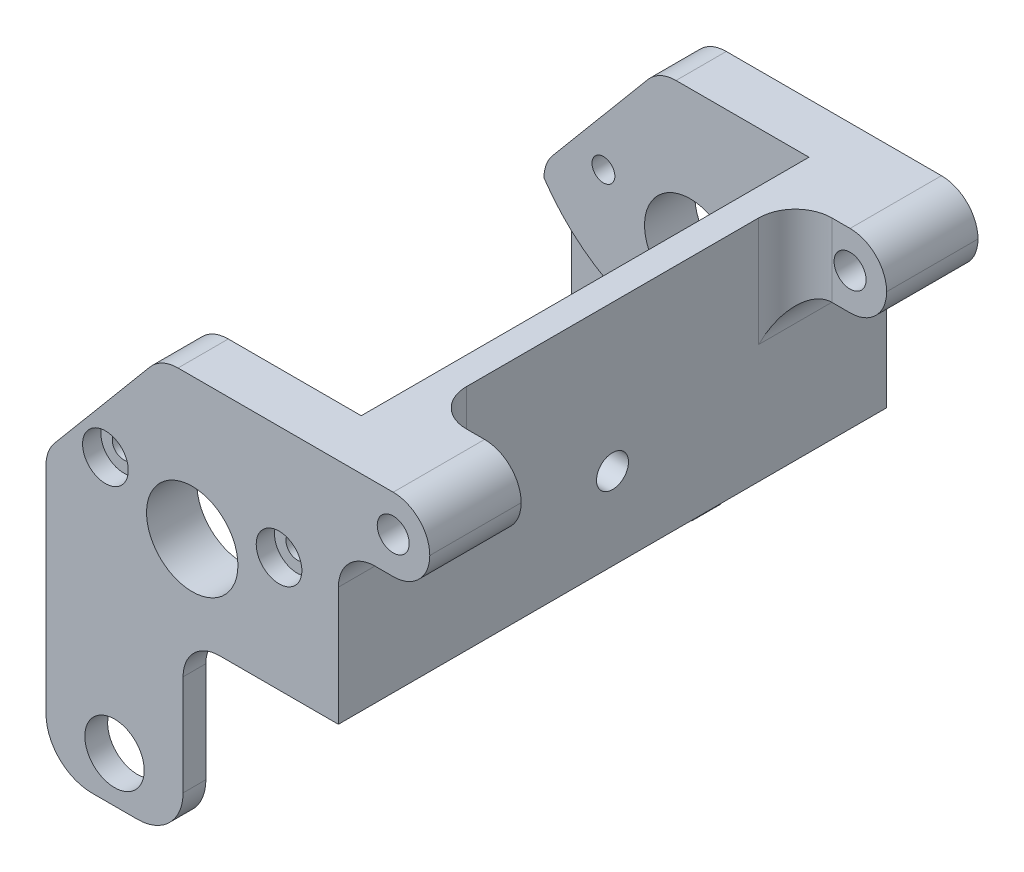
SolidWorks part; units mm, degrees
ref_plane "Front Plane" through (0, 0, 0) normal (0, 0, 1) x (1, 0, 0)
ref_plane "Top Plane" through (0, 0, 0) normal (0, 1, 0) x (1, 0, 0)
ref_plane "Right Plane" through (0, 0, 0) normal (1, 0, 0) x (0, 0, -1)
sketch "Sketch2" plane through (0, 0, 0) normal (0, 0, 1) x (1, 0, 0)
  line L0 (-7.5, 5) -> (-7.5, 30)
  line L1 (-7.5, 30) -> (5.0865, 45)
  line L2 (5.0865, 45) -> (24.5, 45)
  line L3 (24.5, 45) -> (24.5, 20)
  line L4 (24.5, 20) -> (7.5, 20)
  line L5 (7.5, 20) -> (7.5, 5)
  line L6 (-2.5, 0) -> (2.5, 0)
  line L7 (-7.5, 0) -> (7.5, 0) construction
  line L8 (-7.5, 5) -> (7.5, 5) construction
  line L9 (18.0048, 32.5697) -> (-0.9952, 32.5697) construction
  line L10 (8.5048, 32.5697) -> (8.5048, 29.5697) construction
  line L11 (0, 5) -> (8.5048, 29.5697) construction
  circle A5 centre (0, 5) radius 3.25
  circle A6 centre (18.0048, 32.5697) radius 1.25
  circle A7 centre (-0.9952, 32.5697) radius 1.25
  circle A8 centre (8.5048, 29.5697) radius 5
  circle A9 centre (8.5048, 32.5697) radius 12.5 construction
  arc A10 (2.5, 0) -> (7.5, 5) centre (2.5, 5) ccw
  arc A11 (-7.5, 5) -> (-2.5, 0) centre (-2.5, 5) ccw
  dimension "D3" = 6.5
  dimension "D4" = 5
  dimension "D10" = 10
  dimension "D12" = 2.5
  dimension "D14" = 25
  dimension "D15" = 5
  dimension "D1" = 40
  dimension "D2" = 15
  dimension "D5" = 30
  dimension "D6" = 15
  dimension "D7" = 17
  dimension "D8" = 20
  dimension "D9" = 19
  dimension "D11" = 3
  dimension "D13" = 26
extrude "Boss-Extrude1" add sketch "Sketch2" along normal blind 30 and the other way blind 30
sketch "Sketch3" plane through (0, 45, 0) normal (0, 1, 0) x (1, 0, 0)
  line L0 (-7.5, -30) -> (-7.5, 30) construction
  line L1 (-36.5, -27.5) -> (21.5, -27.5)
  line L2 (-36.5, -27.5) -> (-36.5, 27.5)
  line L3 (-36.5, 27.5) -> (21.5, 27.5)
  line L4 (21.5, -27.5) -> (21.5, 27.5)
  line L5 (-36.5, -27.5) -> (21.5, 27.5) construction
  line L6 (-36.5, 27.5) -> (21.5, -27.5) construction
  line L7 (24.5, 30) -> (5.0865, 30) construction
  line L8 (24.5, -30) -> (24.5, 30) construction
  point P0 (-7.5, 0)
  dimension "D1" = 2.5
  dimension "D2" = 3
extrude "Cut-Extrude1" cut sketch "Sketch3" against normal through all
sketch "Sketch4" plane through (24.5, 0, 0) normal (1, 0, 0) x (0, 0, -1)
  line L1 (-30, 45) -> (-20, 45)
  line L2 (-30, 45) -> (-30, 37)
  line L3 (-30, 37) -> (-20, 37)
  line L4 (-20, 45) -> (-20, 37)
  dimension "D1" = 10
  dimension "D2" = 8
extrude "Boss-Extrude2" add sketch "Sketch4" along normal blind 10
fillet "Fillet1" radius 4 2 edges at (34.5, 37, 25) (34.5, 45, 25)
sketch "Sketch5" plane through (0, 0, 20) normal (0, 0, -1) x (-1, 0, 0)
  circle A0 centre (-30.5, 41) radius 1.75
  dimension "D1" = 3.5
extrude "Cut-Extrude2" cut sketch "Sketch5" against normal through all
mirror "Mirror1" about plane through (0, 0, 0) normal (0, 0, 1) of "Cut-Extrude2", "Fillet1", "Boss-Extrude2"
fillet "Fillet2" radius 4 10 edges at (24.5, 41, -20) (24.5, 41, 20) (5.0865, 45, -28.75) (7.5, 20, -28.75) (24.5, 37, -25) (24.5, 37, 25) (7.5, 20, 28.75) (5.0865, 45, 28.75) (-7.5, 30, 28.75) (-7.5, 30, -28.75)
sketch "Sketch6" plane through (0, 0, -27.5) normal (0, 0, 1) x (1, 0, 0)
  line L0 (-0.9952, 32.5697) -> (18.0048, 32.5697) construction
  line L7 (21.5, 45) -> (6.9517, 45)
  line L8 (3.8875, 43.5712) -> (-6.5642, 31.1153)
  line L9 (-7.5, 28.5441) -> (-7.5, 5)
  line L10 (-2.5, 0) -> (2.5, 0)
  line L11 (7.5, 5) -> (7.5, 16)
  line L12 (11.5, 20) -> (21.5, 20)
  line L13 (21.5, 20) -> (21.5, 45)
  line L14 (21.5, 45) -> (6.9517, 45)
  line L15 (3.8875, 43.5712) -> (-6.5642, 31.1153)
  line L19 (11.5, 20) -> (21.5, 20)
  line L20 (21.5, 20) -> (21.5, 45)
  arc A1 (11.5, 20) -> (-7.5, 28.5441) centre (8.8465, 39.497) cw
  circle A2 centre (18.0048, 32.5697) radius 1.25 construction
  circle A3 centre (8.5048, 29.5697) radius 5 construction
  circle A4 centre (-0.9952, 32.5697) radius 1.25 construction
  circle A5 centre (18.0048, 32.5697) radius 1.25
  arc A6 (6.9517, 45) -> (3.8875, 43.5712) centre (6.9517, 41) ccw
  arc A7 (-6.5642, 31.1153) -> (-7.5, 28.5441) centre (-3.5, 28.5441) ccw
  arc A8 (-7.5, 5) -> (-2.5, 0) centre (-2.5, 5) ccw
  arc A9 (2.5, 0) -> (7.5, 5) centre (2.5, 5) ccw
  arc A10 (11.5, 20) -> (7.5, 16) centre (11.5, 16) ccw
  arc A11 (6.9517, 45) -> (3.8875, 43.5712) centre (6.9517, 41) ccw
  arc A12 (-6.5642, 31.1153) -> (-7.5, 28.5441) centre (-3.5, 28.5441) ccw
  circle A16 centre (8.5048, 29.5697) radius 5
  circle A17 centre (-0.9952, 32.5697) radius 1.25
  dimension "D1" = 0
extrude "Boss-Extrude3" add sketch "Sketch6" along normal blind 3
sketch "Sketch7" plane through (0, 0, -30) normal (0, 0, -1) x (-1, 0, 0)
  circle A0 centre (-18.0048, 32.5697) radius 2.5
  circle A1 centre (0.9952, 32.5697) radius 2.5
  dimension "D1" = 5
extrude "Cut-Extrude3" cut sketch "Sketch7" against normal blind 2
mirror "Mirror2" about plane through (0, 0, 0) normal (0, 0, 1) of "Cut-Extrude3", "Boss-Extrude3"
sketch "Sketch8" plane through (24.5, 0, 0) normal (1, 0, 0) x (0, 0, -1)
  line L0 (-20, 41) -> (20, 41) construction
  line L1 (-20, 37) -> (-20, 45) construction
  line L2 (20, 45) -> (20, 37) construction
  line L3 (0, 41) -> (0, 29) construction
  circle A0 centre (0, 29) radius 1.75
  dimension "D1" = 3.5
  dimension "D2" = 12
extrude "Cut-Extrude4" cut sketch "Sketch8" against normal through all
